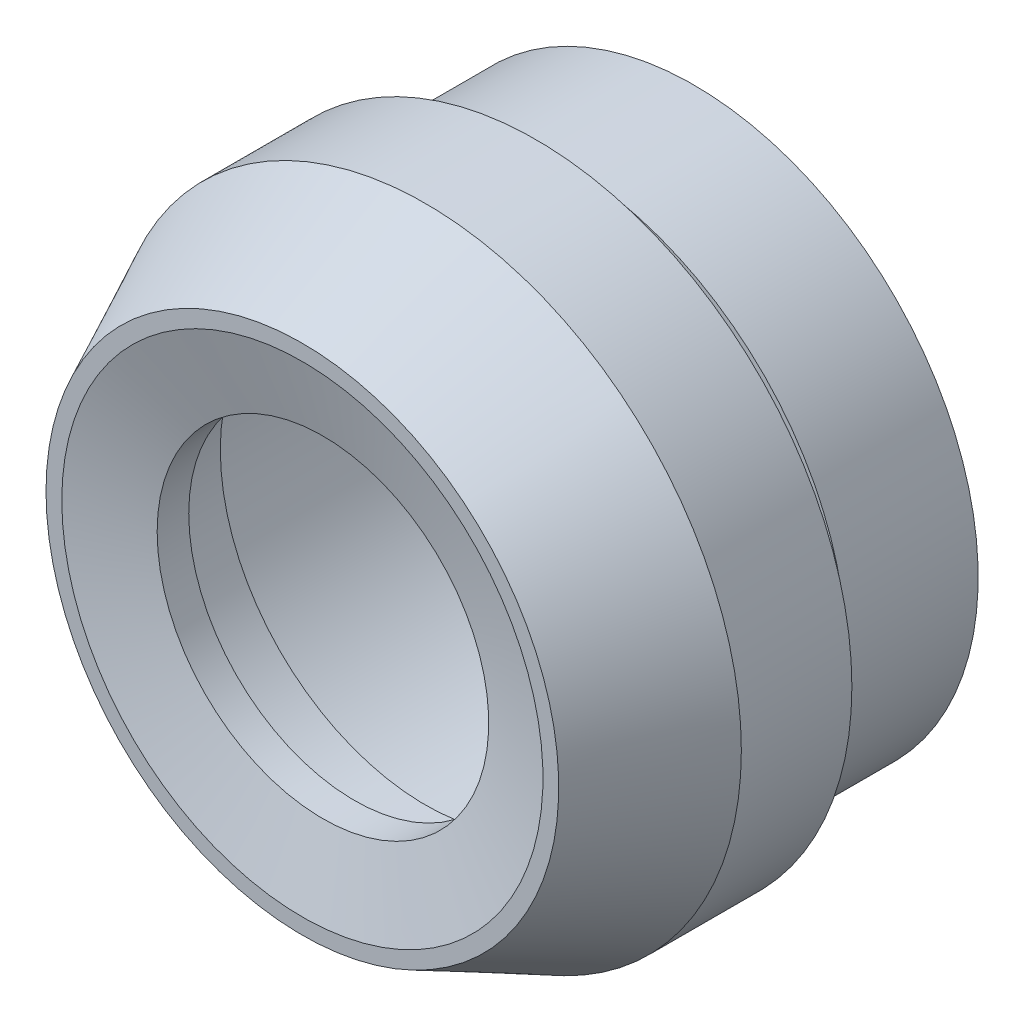
SolidWorks part; units mm, degrees
ref_plane "Ön Düzlem" through (0, 0, 0) normal (0, 0, 1) x (1, 0, 0)
ref_plane "Üst Düzlem" through (0, 0, 0) normal (0, 1, 0) x (1, 0, 0)
ref_plane "Sağ Düzlem" through (0, 0, 0) normal (1, 0, 0) x (0, 0, -1)
ref_axis "Eksen2" through (0, 0, -59.1874) along (0, 0, 1)
sketch "Çizim4" plane through (0, 0, 0) normal (1, 0, 0) x (0, 0, -1)
  line L1 (-24, 32) -> (10, 32)
  line L5 (-24, 32) -> (-24, 26)
  line L10 (-39.6052, 32.4743) -> (-39.6052, 30.4743)
  line L15 (-24, 40) -> (-10, 40)
  line L17 (10, 36) -> (10, 32)
  line L21 (-24, 40) -> (-39.6052, 32.4743)
  line L22 (-10, 40) -> (-10, 35)
  line L23 (-10, 35) -> (-6.7136, 35)
  line L24 (-6.7136, 35) -> (-6.7136, 36)
  line L25 (-6.7136, 36) -> (10, 36)
  line L26 (-24, 26) -> (-34, 26)
  line L27 (-34, 26) -> (-34, 23)
  line L28 (-34, 23) -> (-33, 23)
  line L29 (-33, 23) -> (-33, 21)
  line L30 (-33, 21) -> (-37, 21)
  line L31 (-37, 21) -> (-39.6052, 30.4743)
  dimension "D1" = 14
  dimension "D4" = 2
  dimension "D5" = 6
  dimension "D6" = 4
revolve "Döndür2" add sketch "Çizim4" angle 360 about axis through (0, 0, -59.1874) along (0, 0, 1)
